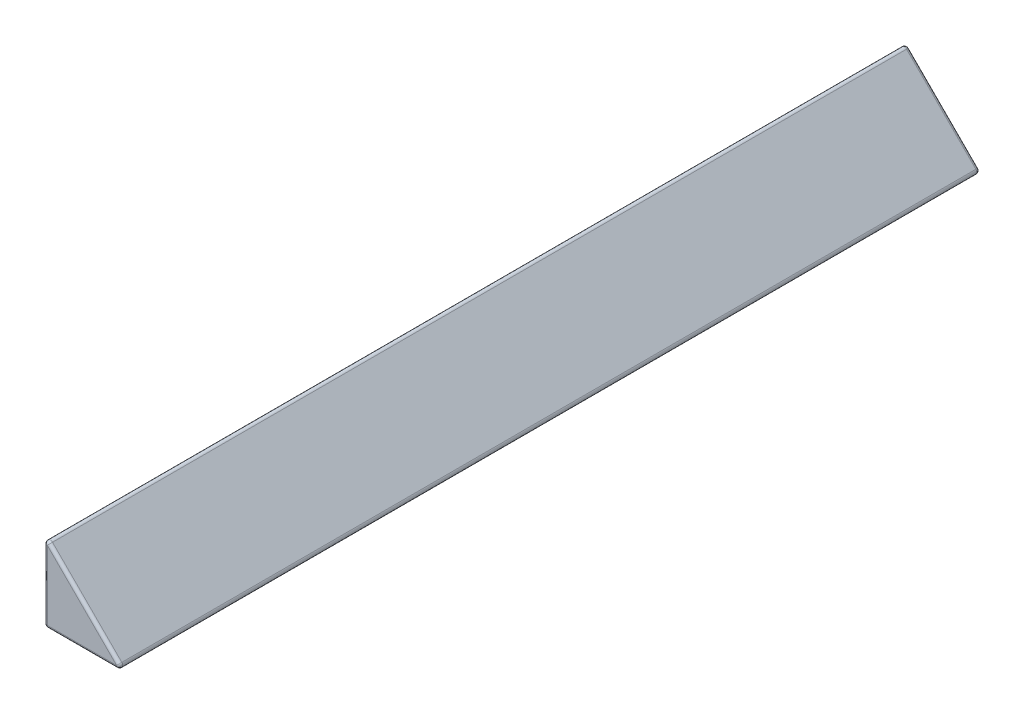
SolidWorks part; units mm, degrees
material "6061-T6 (SS)"
ref_plane "Front Plane" through (0, 0, 0) normal (0, 0, 1) x (1, 0, 0)
ref_plane "Top Plane" through (0, 0, 0) normal (0, 1, 0) x (1, 0, 0)
ref_plane "Right Plane" through (0, 0, 0) normal (1, 0, 0) x (0, 0, -1)
sketch "Sketch1" plane through (0, 0, 0) normal (0, 0, 1) x (1, 0, 0)
  line L0 (0, 0) -> (2.6, 0)
  line L3 (2.6, 0) -> (0, 2.6)
  line L4 (0, 2.6) -> (0, 0)
  line L5 (2.6, 0) -> (2.6, 7.4) construction
  dimension "D1" = 45
extrude "Boss-Extrude1" add sketch "Sketch1" against normal up to surface (28.025 mm away)
fillet "Fillet1" radius 0.1 9 edges at (0, 2.6, -14.0125) (0, 0, -14.0125) (2.6, 0, -14.0125) (1.3, 1.3, -28.025) (0, 1.3, -28.025) (1.3, 0, -28.025) (1.3, 0, 0) (0, 1.3, 0) (1.3, 1.3, 0)
